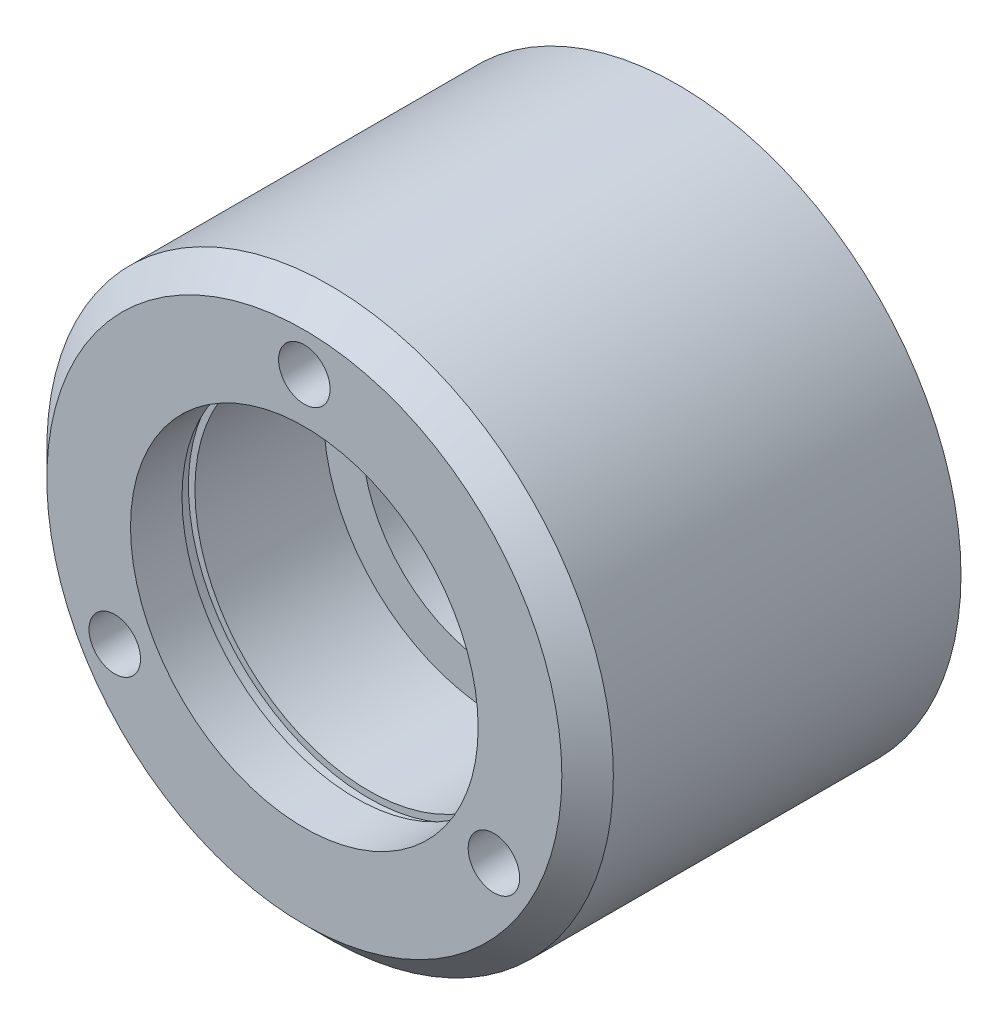
SolidWorks part; units mm, degrees
material "Alliage de zinc AC41A, brut"
ref_plane "Plan de face" through (0, 0, 0) normal (0, 0, 1) x (1, 0, 0)
ref_plane "Plan de dessus" through (0, 0, 0) normal (0, 1, 0) x (1, 0, 0)
ref_plane "Plan de droite" through (0, 0, 0) normal (1, 0, 0) x (0, 0, -1)
sketch "Esquisse1" plane through (0, 0, 0) normal (0, 0, 1) x (1, 0, 0)
  circle A0 centre (0, 0) radius 11
  circle A1 centre (0, 0) radius 5.25
  dimension "D1" = 22
  dimension "D2" = 10.5
extrude "Boss.-Extru.1" add sketch "Esquisse1" along normal blind 7
sketch "Esquisse2" plane through (0, 0, 7) normal (0, 0, 1) x (1, 0, 0)
  circle A0 centre (0, 0) radius 11
  circle A1 centre (0, 0) radius 6.75
  dimension "D1" = 22
  dimension "D2" = 13.5
extrude "Boss.-Extru.2" add sketch "Esquisse2" along normal blind 5
sketch "Esquisse3" plane through (0, 0, 12) normal (0, 0, 1) x (1, 0, 0)
  circle A0 centre (0, 0) radius 7
  circle A1 centre (0, 0) radius 11
  dimension "D1" = 14
  dimension "D2" = 22
extrude "Boss.-Extru.3" add sketch "Esquisse3" along normal blind 0.5
sketch "Esquisse4" plane through (0, 0, 12.5) normal (0, 0, 1) x (1, 0, 0)
  circle A0 centre (0, 0) radius 6.75
  circle A1 centre (0, 0) radius 11
  dimension "D1" = 13.5
  dimension "D2" = 22
extrude "Boss.-Extru.4" add sketch "Esquisse4" along normal blind 2
cosmetic thread "Représentation de filetage2" parameters "D1"=14.5, "D2"=20.5
chamfer "Chanfrein1" distance 1 angle 45 1 edges at (11, 0, 14.5)
sketch "Esquisse7" plane through (0, 0, 0) normal (0, 0, -1) x (-1, 0, 0)
  line L0 (0, 0) -> (0, 8.5) construction
  line L4 (0, 0) -> (7.3612, -4.25) construction
  line L5 (0, 0) -> (-7.3612, -4.25) construction
  point P11 (0, 8.5)
  point P33 (0, 8.5)
  point P49 (7.3612, -4.25)
  point P50 (-7.3612, -4.25)
  dimension "D1" = 8.5
  dimension "D2" = 3
hole_wizard "Diamètre du perçage Ø2.0 (2)1" positions "Esquisse7" profile "Esquisse6" hole size "Ø2.0" standard "ISO" end condition through all
sketch "Esquisse6" plane through (7.3612, -4.25, 0) normal (1, 0, 0) x (0, 1, 0)
  line L0 (0, 0) -> (0, 14.5)
  line L1 (0, 14.5) -> (1, 14.5)
  line L2 (1, 14.5) -> (1, 0)
  line L5 (1, 0) -> (0, 0)
  line L11 (0, -6.35) -> (0, 107.95) construction
  dimension "Diamètre du perçage jusqu'au prochain" = 2
  dimension "Profondeur du perçage jusqu'au prochain" = 14.5
